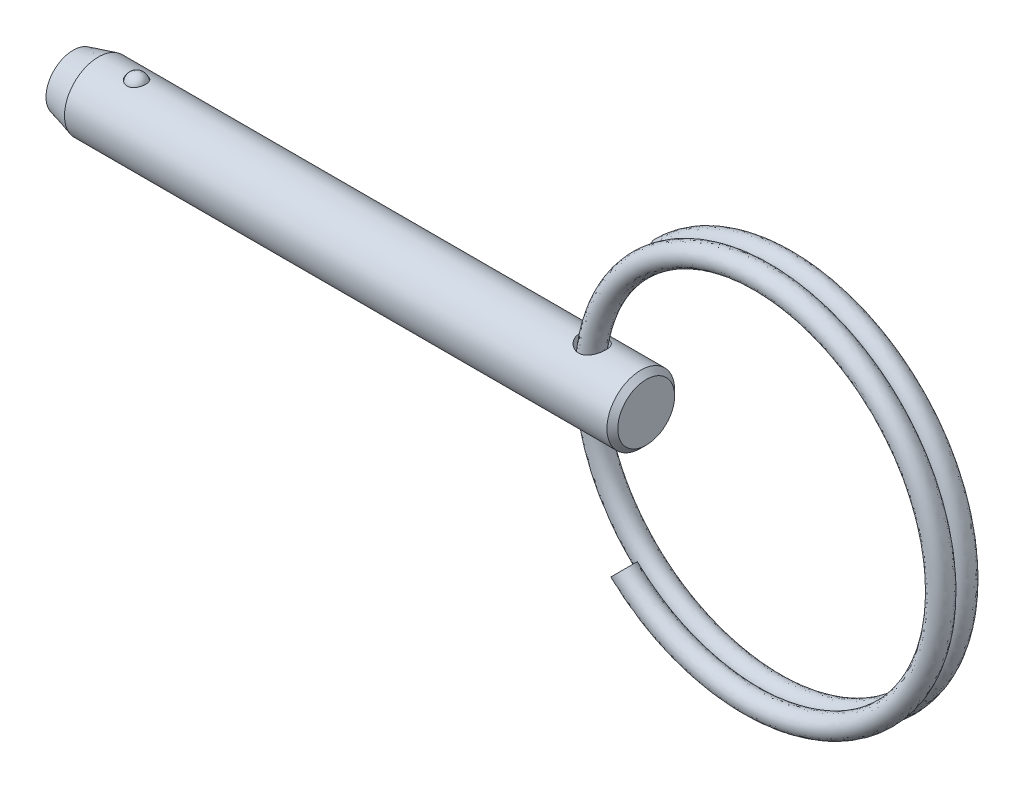
SolidWorks part; units mm, degrees
ref_plane "Front" through (0, 0, 0) normal (0, 0, 1) x (1, 0, 0)
ref_plane "Top" through (0, 0, 0) normal (0, 1, 0) x (1, 0, 0)
ref_plane "Right" through (0, 0, 0) normal (1, 0, 0) x (0, 0, -1)
sketch "Sketch1" plane through (0, 0, 0) normal (0, 0, 1) x (1, 0, 0)
  line L0 (20.1549, 2.0003) -> (19.7739, 2.3813)
  line L1 (19.7739, 2.3813) -> (20.1549, 2.3813) construction
  line L4 (20.1549, 2.0003) -> (20.1549, 0)
  line L5 (20.1549, 2.3813) -> (20.1549, 2.0003) construction
  line L16 (19.7739, 2.3813) -> (-18.3775, 2.3813)
  line L17 (-20.1549, 2.3813) -> (-20.1549, 1.905) construction
  line L19 (-18.3775, 2.3813) -> (-20.1549, 2.3813) construction
  line L22 (-20.1549, -2.3813) -> (-18.3775, -2.3812) construction
  line L23 (-15.6875, 2.1431) -> (-15.6875, -2.1431) construction
  line L24 (-20.1549, 0) -> (20.1549, 0)
  line L27 (20.1549, 0) -> (22.1552, 0) construction
  line L29 (-20.1549, 0) -> (-20.1549, -1.905) construction
  line L36 (15.4051, 0) -> (15.4051, 2.3813) construction
  line L37 (-20.1549, 1.905) -> (-20.1549, 0)
  line L38 (-18.3775, -2.3812) -> (20.1549, -2.3813) construction
  line L39 (-20.1549, -1.905) -> (-20.1549, -2.3813) construction
  line L40 (-18.3775, 2.3813) -> (-20.1549, 1.905)
  line L42 (-18.3775, -2.3812) -> (-20.1549, -1.905) construction
  line L43 (-18.3775, 2.3813) -> (-18.3775, -2.3812) construction
  circle A2 centre (-15.6875, 2.1431) radius 0.6572 construction
  point P35 (-15.0749, 2.3813)
  dimension "D2" = 4.2863
  dimension "D11" = 0.4191
  dimension "A" = 4.7625
  dimension "D" = 4.7498
  dimension "E" = 5.1816
  dimension "D3" = 0.381
  dimension "Useable Length" = 30.48
  dimension "D12" = 3.81
  dimension "C" = 5.08
  dimension "A1" = 15
revolve "Revolve1" add sketch "Sketch1" angle 360 about L27
sketch "Sketch2" plane through (0, 0, 0) normal (0, 0, 1) x (1, 0, 0)
  line L0 (-15.0048, 2.1431) -> (-16.3701, 2.1431)
  line L1 (-15.6875, 2.8003) -> (-15.6875, 2.8257) construction
  line L2 (-15.0048, 2.1431) -> (-13.6396, 2.1431) construction
  circle A0 centre (-15.6875, 2.1431) radius 0.6572 construction
  circle A1 centre (-15.6875, 2.1431) radius 0.6572 construction
  arc A2 (-16.3701, 2.1431) -> (-15.0048, 2.1431) centre (-15.6875, 2.1431) cw
  dimension "D1" = 0.0254
revolve "Cut-Revolve1" cut sketch "Sketch2" angle 360 about L2
sketch "Sketch3" plane through (0, 0, 0) normal (0, 0, 1) x (1, 0, 0)
  line L0 (-15.0302, 2.1431) -> (-16.3447, 2.1431)
  line L1 (-15.0302, 2.1431) -> (-13.7158, 2.1431) construction
  circle A0 centre (-15.6875, 2.1431) radius 0.6572 construction
  arc A1 (-15.0302, 2.1431) -> (-16.3447, 2.1431) centre (-15.6875, 2.1431) ccw
revolve "Revolve2" add sketch "Sketch3" angle 360 about L1
sketch "Sketch4" plane through (0, 0, 0) normal (0, 0, 1) x (1, 0, 0)
  line L1 (16.3576, -2.3812) -> (17.3101, -2.3812)
  line L2 (16.3576, -2.3812) -> (16.3576, 2.3812)
  line L3 (16.3576, 2.3812) -> (17.3101, 2.3812)
  line L4 (17.3101, -2.3812) -> (17.3101, 2.3812)
  line L5 (16.3576, -2.3812) -> (16.3576, -3.3338) construction
  line L6 (17.3101, 2.3812) -> (20.1549, 2.3813) construction
  line L8 (15.4051, -2.3812) -> (15.4051, 2.3812) construction
  line L9 (15.4051, 0) -> (16.3576, 0) construction
  line L11 (16.3576, 0) -> (17.3101, 0) construction
  line L12 (19.7739, 2.3813) -> (-18.3775, 2.3813) construction
  line L14 (-18.3775, -2.3812) -> (20.1549, -2.3812) construction
  dimension "D1" = 1.905
revolve "Cut-Revolve2" cut sketch "Sketch4" angle 360 about L2
sketch "Sketch5" plane through (0, 0, 0) normal (0, 0, 1) x (1, 0, 0)
  line L0 (0, 0) -> (15.4756, 0) construction
  line L1 (15.4756, 0) -> (15.4756, 2.3813) construction
  line L2 (19.7739, 2.3813) -> (-18.3775, 2.3813) construction
  line L3 (28.9376, 0) -> (42.3996, 0) construction
  line L4 (17.3101, 2.3812) -> (17.2396, 2.3813) construction
  line L5 (16.3576, 2.3812) -> (17.3101, 2.3812) construction
  line L6 (15.6879, 2.3812) -> (15.6879, -2.3812) construction
  line L7 (15.4756, 2.3813) -> (15.4051, 2.3813) construction
  line L8 (16.3576, -2.3812) -> (17.3101, -2.3812) construction
  line L9 (15.6879, -2.3812) -> (17.3101, -2.3812) construction
  line L10 (15.4756, 0) -> (28.9376, 0) construction
  line L12 (17.2396, 2.3813) -> (15.6879, 2.3812) construction
  line L13 (28.9376, 11.938) -> (28.9376, 13.462) construction
  circle A0 centre (28.9376, 0) radius 13.462
  circle A1 centre (28.9376, 0) radius 11.938 construction
  circle A2 centre (28.9376, 0) radius 12.7 construction
  point P26 (28.9376, 12.7)
  dimension "R Ring Dia" = 25.4
  dimension "Ring OD" = 1.524
curve "Helix/Spiral1" pitch 1.5494 height 1.3557 radius 13.462 left hand yes centre (28.9376, 0, 0) axis (0, 0, -1) start towards (1, 0, 0)
sketch "Sketch6" plane through (114.0038, 0, 0) normal (0, 1, 0) x (0, 0, -1)
  line L0 (0, 97.0042) -> (0, 97.7662) construction
  line L1 (0, 97.7662) -> (0, 98.5282) construction
  circle A0 centre (0, 97.7662) radius 0.762
  dimension "D1" = 1.524
sketch "Sketch7" plane through (0, 0, 0) normal (0, 0, 1) x (1, 0, 0)
  circle A0 centre (28.9376, 0) radius 13.462 construction
  circle A1 centre (28.9376, 0) radius 13.462
curve "Helix/Spiral2" pitch 1.5494 height 1.3557 radius 13.462 left hand yes centre (28.9376, 0, 0) axis (0, 0, 1) start towards (1, 0, 0)
sweep "Sweep1" add profiles "Sketch6" path "Helix/Spiral1"
sweep "Sweep2" add profiles "Sketch6<2>" path "Helix/Spiral2"
sketch "Sketch6<2>" plane through (114.0038, 0, 0) normal (0, 1, 0) x (0, 0, -1) same geometry as "Sketch6"
equation "\"D12@Sketch1\"=\"A@Sketch1\" * 0.80"
equation "\"D2@Sketch1\"=\"A@Sketch1\" * 0.9"
equation "\"D1@Sketch4\" = \"A@Sketch1\" / 2.5"
equation "\"Ring OD@Sketch5\" = \"R Ring Dia@Sketch5\" * 0.06"
equation "\"D4@Helix/Spiral1\"=\"Ring OD@Sketch5\" + 0.001"
equation "\"D1@Sketch6\"=\"Ring OD@Sketch5\""
equation "\"D4@Helix/Spiral2\" = \"D4@Helix/Spiral1\""
equation "\"D5@Helix/Spiral2\" = \"D5@Helix/Spiral1\""
